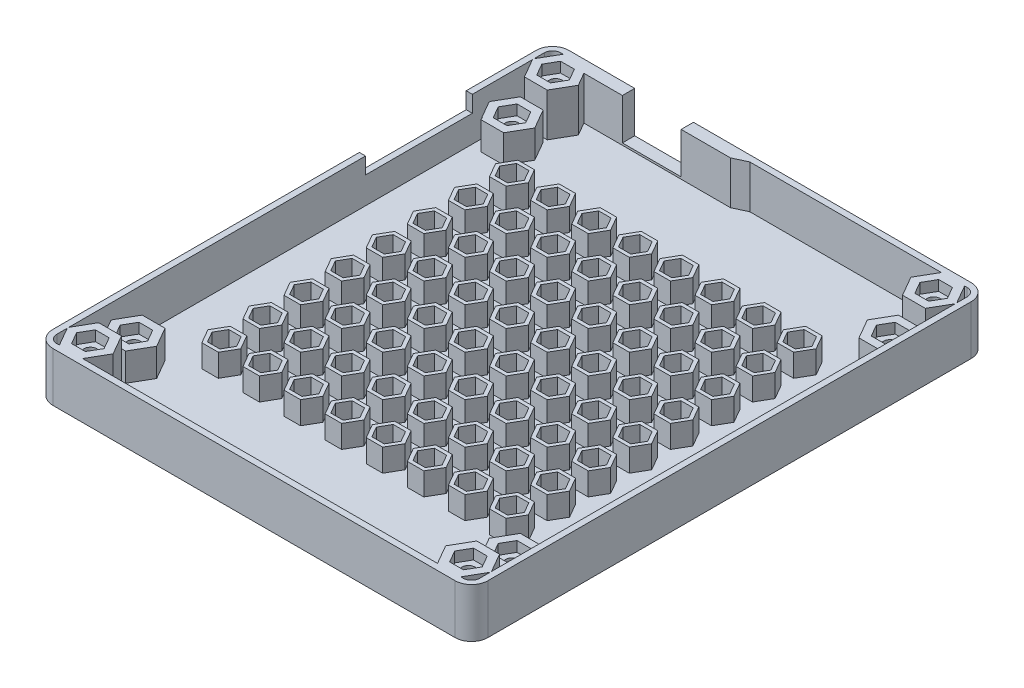
SolidWorks part; units mm, degrees
ref_plane "Přední rovina" through (0, 0, 0) normal (0, 0, 1) x (1, 0, 0)
ref_plane "Horní rovina" through (0, 0, 0) normal (0, 1, 0) x (1, 0, 0)
ref_plane "Pravá rovina" through (0, 0, 0) normal (1, 0, 0) x (0, 0, -1)
sketch "Skica1" plane through (0, 0, 0) normal (0, 1, 0) x (1, 0, 0)
  line L0 (0, 0) -> (-100, 100) construction
  line L1 (-50, 50) -> (50, 50) construction
  line L2 (-50, 50) -> (-50, -50) construction
  line L3 (-50, -50) -> (50, -50) construction
  line L4 (50, 50) -> (50, -50) construction
  line L5 (-50, 50) -> (50, -50) construction
  line L6 (-50, -50) -> (50, 50) construction
  line L7 (-47.6743, 43.1) -> (-44.3257, 43.1)
  line L8 (-44.3257, 43.1) -> (-42.6514, 46)
  line L9 (-42.6514, 46) -> (-44.3257, 48.9)
  line L10 (-44.3257, 48.9) -> (-47.6743, 48.9)
  line L11 (-47.6743, 48.9) -> (-49.3486, 46)
  line L12 (-49.3486, 46) -> (-47.6743, 43.1)
  line L13 (-48.7713, 41.2) -> (-43.2287, 41.2)
  line L14 (-43.2287, 41.2) -> (-40.4574, 46)
  line L15 (-40.4574, 46) -> (-43.2287, 50.8)
  line L16 (-43.2287, 50.8) -> (-48.7713, 50.8)
  line L17 (-48.7713, 50.8) -> (-51.5426, 46)
  line L18 (-51.5426, 46) -> (-48.7713, 41.2)
  line L19 (0, 81.3987) -> (0, -91.9033) construction
  line L20 (-42.6514, 56.6) -> (-44.3257, 59.5)
  line L21 (-44.3257, 59.5) -> (-47.6743, 59.5)
  line L22 (-47.6743, 59.5) -> (-49.3486, 56.6)
  line L23 (-49.3486, 56.6) -> (-47.6743, 53.7)
  line L24 (-47.6743, 53.7) -> (-44.3257, 53.7)
  line L25 (-44.3257, 53.7) -> (-42.6514, 56.6)
  line L26 (-48.7713, 51.8) -> (-43.2287, 51.8)
  line L27 (-43.2287, 51.8) -> (-40.4574, 56.6)
  line L28 (-40.4574, 56.6) -> (-43.2287, 61.4)
  line L29 (-43.2287, 61.4) -> (-48.7713, 61.4)
  line L30 (-48.7713, 61.4) -> (-51.5426, 56.6)
  line L31 (-51.5426, 56.6) -> (-48.7713, 51.8)
  line L36 (74.9355, -74.9355) -> (-74.9355, 74.9355) construction
  line L37 (74.9355, 74.9355) -> (-74.9355, -74.9355) construction
  line L38 (-52.9426, -62.8) -> (52.9426, -62.8)
  line L39 (-52.9426, -62.8) -> (-52.9426, 62.8)
  line L40 (-52.9426, 62.8) -> (52.9426, 62.8)
  line L41 (52.9426, -62.8) -> (52.9426, 62.8)
  line L42 (-52.9426, -62.8) -> (52.9426, 62.8) construction
  line L43 (-52.9426, 62.8) -> (52.9426, -62.8) construction
  line L44 (-106.951, 0) -> (125.2961, 0) construction
  line L45 (-46, 37.8836) -> (-46, 68.4593) construction
  line L47 (-51.4426, -61.3) -> (51.4426, -61.3)
  line L48 (-51.4426, -61.3) -> (-51.4426, 61.3)
  line L49 (-51.4426, 61.3) -> (51.4426, 61.3)
  line L50 (51.4426, -61.3) -> (51.4426, 61.3)
  line L51 (-51.4426, -61.3) -> (51.4426, 61.3) construction
  line L52 (-51.4426, 61.3) -> (51.4426, -61.3) construction
  circle A0 centre (-46, 46) radius 2.9 construction
  circle A1 centre (-46, 46) radius 4.8 construction
  circle A2 centre (-46, 56.6) radius 2.9 construction
  circle A3 centre (-46, 56.6) radius 4.8 construction
  circle A4 centre (-46, 46) radius 1.6
  circle A5 centre (-46, 56.6) radius 1.6
  point P0 (0, 0)
  point P7 (-41.8431, 43.6)
  dimension "D9" = 1.5
  dimension "D10" = 1.5
  dimension "D11" = 0.1
  dimension "D12" = 0.1
  dimension "D13" = 3.2
  dimension "D14" = 3.2
  dimension "D1" = 100
  dimension "D2" = 100
  dimension "D3" = 5.8
  dimension "D4" = 4
  dimension "D5" = 9.6
  dimension "D6" = 5.8
  dimension "D7" = 9.6
  dimension "D8" = 1
extrude "Přidat vysunutím25" add sketch "Skica1" against normal blind 3 contours L49 L48 L30 | L20 L21 L22 L23 L24 L25 | L7 L8 L9 L10 L11 L12 | L48 L47 L50 L49 | L13 L14 L15 L16 L17 L18 | L26 L27 L28 L29 L30 L31 region at (-50.5714, 0, -59.7911)
extrude "Přidat vysunutím26" add sketch "Skica1<21>" against normal blind 3 and the other way blind 10.5 contours L38 L41 L40 L39 L50 L47 L48 L18 L17 L31 L30 L49 L29 L28 | L18 L48 L17 | L31 L48 L30 | L30 L49 L28 L29 region at (-51.4759, 0, -46) region at (-51.4759, 0, -56.6) region at (-46, 0, -61.3498) region at (-52.7783, 0, 0)
sketch "Skica1<21>" plane through (0, 0, 0) normal (0, 1, 0) x (1, 0, 0) same geometry as "Skica1"
extrude "Přidat vysunutím28" add sketch "Skica1<23>" along normal blind 6.8 contours L48 L18 L13 L14 L15 L16 L17 L12 L11 L10 L9 L8 L7 | L18 L48 L17 region at (-49.9806, 0, -43.5863) region at (-51.4759, 0, -46)
sketch "Skica1<23>" plane through (0, 0, 0) normal (0, 1, 0) x (1, 0, 0) same geometry as "Skica1"
extrude "Přidat vysunutím29" add sketch "Skica1<24>" along normal blind 4.3 contours L11 L12 L7 L8 L9 L10 region at (-48.4347, 0, -44.5943)
sketch "Skica1<24>" plane through (0, 0, 0) normal (0, 1, 0) x (1, 0, 0) same geometry as "Skica1"
pattern_linear "LinPole3" count 2 spacing 92 along (1, 0, 0) count 2 spacing 92 along (0, 0, 1) of "Přidat vysunutím28", "Přidat vysunutím29"
extrude "Přidat vysunutím30" add sketch "Skica1<25>" along normal blind 10.5 contours L49 L30 L48 L31 L26 L27 L28 L25 L24 L23 L22 L21 L20 | L30 L49 L28 L29 | L31 L48 L30 region at (-51.2973, 0, -56.6) region at (-51.4759, 0, -56.6) region at (-46, 0, -61.3498)
sketch "Skica1<25>" plane through (0, 0, 0) normal (0, 1, 0) x (1, 0, 0) same geometry as "Skica1"
extrude "Přidat vysunutím31" add sketch "Skica1<26>" along normal blind 8 contours L24 L25 L20 L21 L22 L23 A5 region at (-43.5653, 0, -55.1943)
sketch "Skica1<26>" plane through (0, 0, 0) normal (0, 1, 0) x (1, 0, 0) same geometry as "Skica1"
pattern_linear "LinPole4" count 2 spacing 92 along (1, 0, 0) count 2 spacing 113.2 along (0, 0, 1) of "Přidat vysunutím31", "Přidat vysunutím30"
fillet "Zaoblit4" radius 4 4 edges at (-52.9426, 3.75, 62.8) (52.9426, 3.75, 62.8) (52.9426, 3.75, -62.8) (-52.9426, 3.75, -62.8)
sketch "Skica9" plane through (-52.9426, 0, 0) normal (-1, 0, 0) x (0, 0, 1)
  line L0 (58.8, 10.5) -> (-58.8, 10.5) construction
  line L1 (-15.8, 6.5) -> (-41.8, 6.5)
  line L2 (-15.8, 6.5) -> (-15.8, 10.5)
  line L3 (-15.8, 10.5) -> (-41.8, 10.5)
  line L4 (-41.8, 6.5) -> (-41.8, 10.5)
  line L5 (-15.8, 6.5) -> (-41.8, 10.5) construction
  line L6 (-15.8, 10.5) -> (-41.8, 6.5) construction
  line L7 (-62.8, -3) -> (-62.8, 10.5) construction
  point P0 (-28.8, 8.5)
  dimension "D1" = 26
  dimension "D2" = 21
  dimension "D3" = 4
extrude "Odebrat vysunutím1" cut sketch "Skica9" against normal blind 4 contours L4 L3 L2 L1
sketch "Skica10" plane through (0, 0, -62.8) normal (0, 0, -1) x (-1, 0, 0)
  line L0 (48.9426, 10.5) -> (-48.9426, 10.5) construction
  line L1 (18.6426, 0.5) -> (32.9426, 0.5)
  line L2 (18.6426, 0.5) -> (18.6426, 10.5)
  line L3 (18.6426, 10.5) -> (32.9426, 10.5)
  line L4 (32.9426, 0.5) -> (32.9426, 10.5)
  line L5 (52.9426, 10.5) -> (52.9426, -3) construction
  dimension "D1" = 10
  dimension "D2" = 14.3
  dimension "D3" = 20
extrude "Odebrat vysunutím2" cut sketch "Skica10" against normal blind 5
sketch "Skica11" plane through (0, 0, 0) normal (0, 1, 0) x (1, 0, 0)
  line L0 (-43.171, 61.3) -> (43.171, 61.3) construction
  line L1 (-35, -35) -> (35, -35) construction
  line L2 (-35, -35) -> (-35, 35) construction
  line L3 (-35, 35) -> (35, 35) construction
  line L4 (35, -35) -> (35, 35) construction
  line L5 (-35, -35) -> (35, 35) construction
  line L6 (-35, 35) -> (35, -35) construction
  line L7 (-33.5, 32.4019) -> (-32, 35)
  line L8 (-32, 35) -> (-33.5, 37.5981)
  line L9 (-33.5, 37.5981) -> (-36.5, 37.5981)
  line L10 (-36.5, 37.5981) -> (-38, 35)
  line L11 (-38, 35) -> (-36.5, 32.4019)
  line L12 (-36.5, 32.4019) -> (-33.5, 32.4019)
  line L13 (-33, 31.5359) -> (-31, 35)
  line L14 (-31, 35) -> (-33, 38.4641)
  line L15 (-33, 38.4641) -> (-37, 38.4641)
  line L16 (-37, 38.4641) -> (-39, 35)
  line L17 (-39, 35) -> (-37, 31.5359)
  line L18 (-37, 31.5359) -> (-33, 31.5359)
  circle A0 centre (-35, 35) radius 2.5981 construction
  circle A1 centre (-35, 35) radius 3.4641 construction
  point P0 (0, 0)
  dimension "D1" = 70
  dimension "D2" = 3
  dimension "D3" = 4
extrude "Přidat vysunutím32" add sketch "Skica11" along normal blind 5.5
pattern_linear "LinPole5" count 8 spacing 10 along (1, 0, 0) count 8 spacing 10 along (0, 0, 1) of "Přidat vysunutím32"
sketch "Skica12" plane through (52.9426, 0, 0) normal (1, 0, 0) x (0, 0, -1)
  line L0 (-58.8, -3) -> (58.8, -3) construction
  line L1 (-68.1521, -1.5) -> (66.6031, -1.5)
  line L2 (-68.1521, -1.5) -> (-68.1521, -12.5491)
  line L3 (-68.1521, -12.5491) -> (66.6031, -12.5491)
  line L4 (66.6031, -1.5) -> (66.6031, -12.5491)
  dimension "D1" = 1.5
extrude "Odebrat vysunutím3" cut sketch "Skica12" against normal through all
fillet "Zaoblit5" radius 2 4 edges at (-51.4426, 5.25, 61.3) (51.4426, 5.25, 61.3) (51.4426, 5.25, -61.3) (-51.4426, 5.25, -61.3)
sketch "Skica13" plane through (0, 0, -61.3) normal (0, 0, 1) x (1, 0, 0)
  line L0 (-32.9426, 10.5) -> (-43.9426, 10.5)
  line L1 (-43.171, 10.5) -> (-32.9426, 10.5) construction
  line L2 (-43.9426, 10.5) -> (-43.9426, 0)
  line L3 (-43.171, 0) -> (43.171, 0) construction
  line L4 (-43.9426, 0) -> (-6.6426, 0)
  line L5 (-6.6426, 0) -> (-6.6426, 10.5)
  line L6 (-18.6426, 10.5) -> (43.171, 10.5) construction
  line L7 (-6.6426, 10.5) -> (-18.6426, 10.5)
  line L8 (-18.6426, 10.5) -> (-18.6426, 0.5)
  line L9 (-18.6426, 0.5) -> (-32.9426, 0.5)
  line L10 (-32.9426, 0.5) -> (-32.9426, 10.5)
  dimension "D1" = 11
  dimension "D2" = 12
extrude "Přidat vysunutím33" add sketch "Skica13" along normal blind 1.5
sketch "Skica14" plane through (0, 10.5, 0) normal (0, 1, 0) x (1, 0, 0)
  line L5 (-6.6426, 59.8) -> (-6.6426, 61.3)
  line L6 (-6.6426, 61.3) -> (43.171, 61.3) construction
  line L7 (-6.6426, 59.8) -> (-6.6426, 61.3) construction
  line L8 (-6.6426, 61.3) -> (-3.4258, 61.3)
  line L9 (-3.4258, 61.3) -> (-6.6426, 59.8)
  dimension "D1" = 25
extrude "Přidat vysunutím34" add sketch "Skica14" against normal up to next contours L9 L5 L8
